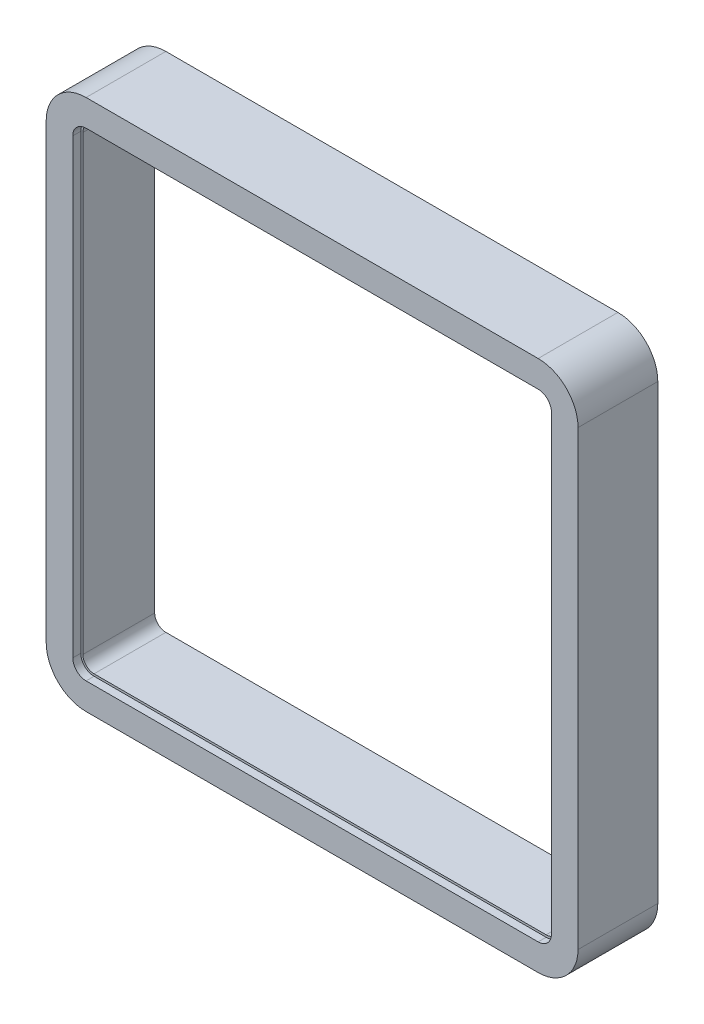
SolidWorks part; units mm, degrees
ref_plane "Piano frontale" through (0, 0, 0) normal (0, 0, 1) x (1, 0, 0)
ref_plane "Piano superiore" through (0, 0, 0) normal (0, 1, 0) x (1, 0, 0)
ref_plane "Piano destro" through (0, 0, 0) normal (1, 0, 0) x (0, 0, -1)
sketch "Sketch1" plane through (0, 0, 0) normal (0, 0, 1) x (1, 0, 0)
  line L5 (-100, -100) -> (100, -100)
  line L6 (-100, -100) -> (-100, 100)
  line L7 (-100, 100) -> (100, 100)
  line L8 (100, -100) -> (100, 100)
  line L9 (-100, -100) -> (100, 100) construction
  line L10 (-100, 100) -> (100, -100) construction
  point P0 (0, 0)
  dimension "D1" = 200
extrude "Boss-Extrude1" add sketch "Sketch1" along normal blind 30
fillet "Fillet1" radius 15 4 edges at (100, -100, 15) (-100, -100, 15) (100, 100, 15) (-100, 100, 15)
sketch "Sketch2" plane through (0, 0, 30) normal (0, 0, 1) x (1, 0, 0)
  line L0 (-85, -90) -> (85, -90)
  line L1 (90, -85) -> (90, 85)
  line L2 (85, 90) -> (-85, 90)
  line L3 (-90, 85) -> (-90, -85)
  line L14 (-85, -100) -> (85, -100)
  line L15 (100, -85) -> (100, 85)
  line L16 (85, 100) -> (-85, 100)
  line L17 (-100, 85) -> (-100, -85)
  line L18 (-85, -100) -> (85, -100) construction
  line L19 (100, -85) -> (100, 85) construction
  line L20 (85, 100) -> (-85, 100) construction
  line L21 (-100, 85) -> (-100, -85) construction
  arc A0 (85, -90) -> (90, -85) centre (85, -85) ccw
  arc A1 (90, 85) -> (85, 90) centre (85, 85) ccw
  arc A2 (-85, 90) -> (-90, 85) centre (-85, 85) ccw
  arc A3 (-90, -85) -> (-85, -90) centre (-85, -85) ccw
  arc A15 (85, -100) -> (100, -85) centre (85, -85) ccw
  arc A16 (100, 85) -> (85, 100) centre (85, 85) ccw
  arc A17 (-85, 100) -> (-100, 85) centre (-85, 85) ccw
  arc A18 (-100, -85) -> (-85, -100) centre (-85, -85) ccw
  arc A19 (85, -100) -> (100, -85) centre (85, -85) ccw construction
  arc A20 (100, 85) -> (85, 100) centre (85, 85) ccw construction
  arc A21 (-85, 100) -> (-100, 85) centre (-85, 85) ccw construction
  arc A22 (-100, -85) -> (-85, -100) centre (-85, -85) ccw construction
  dimension "D1" = 0
  dimension "D2" = 10
extrude "Cut-Extrude2" cut sketch "Sketch2" against normal blind 3
sketch "Sketch3" plane through (0, 0, 27) normal (0, 0, 1) x (1, 0, 0)
  line L4 (-85, -89.2) -> (85, -89.2)
  line L5 (89.2, -85) -> (89.2, 85)
  line L6 (85, 89.2) -> (-85, 89.2)
  line L7 (-89.2, 85) -> (-89.2, -85)
  line L8 (-85, -90) -> (85, -90)
  line L9 (90, -85) -> (90, 85)
  line L10 (85, 90) -> (-85, 90)
  line L11 (-90, 85) -> (-90, -85)
  line L12 (-85, -90) -> (85, -90) construction
  line L13 (90, -85) -> (90, 85) construction
  line L14 (85, 90) -> (-85, 90) construction
  line L15 (-90, 85) -> (-90, -85) construction
  arc A4 (85, -89.2) -> (89.2, -85) centre (85, -85) ccw
  arc A5 (89.2, 85) -> (85, 89.2) centre (85, 85) ccw
  arc A6 (-85, 89.2) -> (-89.2, 85) centre (-85, 85) ccw
  arc A7 (-89.2, -85) -> (-85, -89.2) centre (-85, -85) ccw
  arc A8 (-90, -85) -> (-85, -90) centre (-85, -85) ccw
  arc A9 (85, -90) -> (90, -85) centre (85, -85) ccw
  arc A10 (90, 85) -> (85, 90) centre (85, 85) ccw
  arc A11 (-85, 90) -> (-90, 85) centre (-85, 85) ccw
  arc A12 (-90, -85) -> (-85, -90) centre (-85, -85) ccw construction
  arc A13 (85, -90) -> (90, -85) centre (85, -85) ccw construction
  arc A14 (90, 85) -> (85, 90) centre (85, 85) ccw construction
  arc A15 (-85, 90) -> (-90, 85) centre (-85, 85) ccw construction
  dimension "D1" = 0
  dimension "D2" = 0.8
extrude "Cut-Extrude3" cut sketch "Sketch3" against normal through all
ref_plane "Plane1" through (-89.2, 85, 0) normal (0, -1, 0) x (-1, 0, 0)
